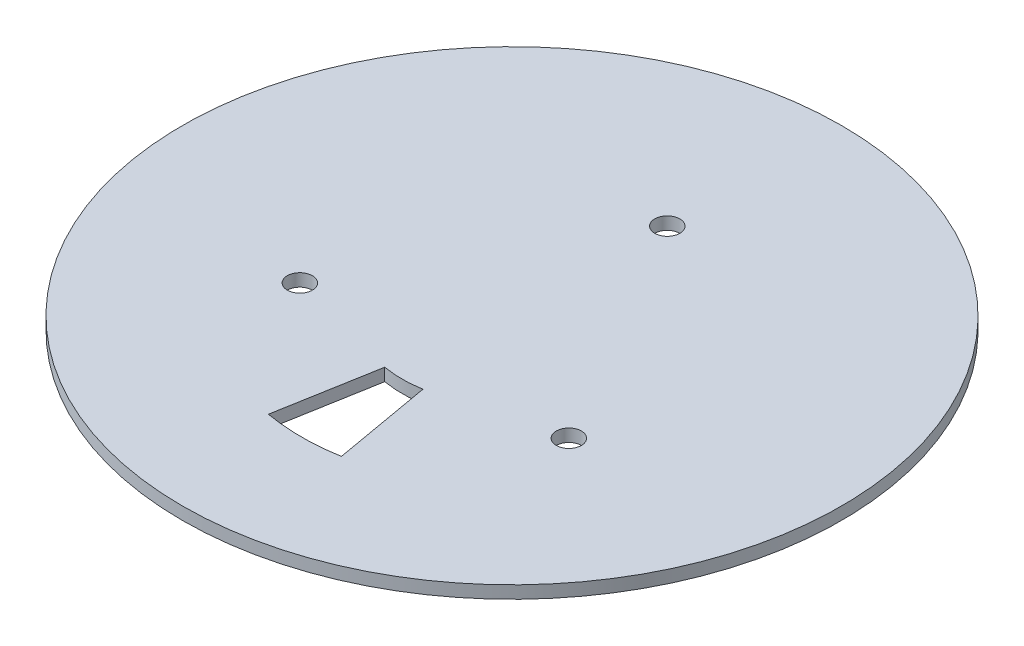
SolidWorks part; units mm, degrees
ref_plane "Plano frontal" through (0, 0, 0) normal (0, 0, 1) x (1, 0, 0)
ref_plane "Plano superior" through (0, 0, 0) normal (0, 1, 0) x (1, 0, 0)
ref_plane "Plano direito" through (0, 0, 0) normal (1, 0, 0) x (0, 0, -1)
sketch "Esboço1" plane through (0, 0, 0) normal (0, 1, 0) x (1, 0, 0)
  circle A0 centre (0, 0) radius 105
  dimension "D1" = 210
extrude "Ressalto-extrusão1" add sketch "Esboço1" along normal blind 4
sketch "Esboço2" plane through (0, 4, 0) normal (0, 1, 0) x (1, 0, 0)
  line L0 (-6.0777, -34.4683) -> (-11.6344, -65.9821) construction
  line L1 (6.0777, -34.4683) -> (11.6344, -65.9821) construction
  line L2 (-6.0777, -34.4683) -> (-11.6344, -65.9821)
  line L3 (6.0777, -34.4683) -> (11.6344, -65.9821)
  arc A0 (-11.6344, -65.9821) -> (11.6344, -65.9821) centre (0, 0) ccw construction
  arc A1 (-6.0777, -34.4683) -> (6.0777, -34.4683) centre (0, 0) ccw construction
  arc A2 (-11.6344, -65.9821) -> (11.6344, -65.9821) centre (0, 0) ccw
  arc A3 (-6.0777, -34.4683) -> (6.0777, -34.4683) centre (0, 0) ccw
extrude "Corte-extrusão1" cut sketch "Esboço2" against normal through all
sketch "Esboço3" plane through (0, 4, 0) normal (0, 1, 0) x (1, 0, 0)
  circle A0 centre (42.8509, -24.74) radius 4 construction
  circle A1 centre (0, 49.48) radius 4 construction
  circle A2 centre (-42.8509, -24.74) radius 4 construction
  circle A3 centre (42.8509, -24.74) radius 4
  circle A4 centre (0, 49.48) radius 4
  circle A5 centre (-42.8509, -24.74) radius 4
extrude "Corte-extrusão2" cut sketch "Esboço3" against normal through all
